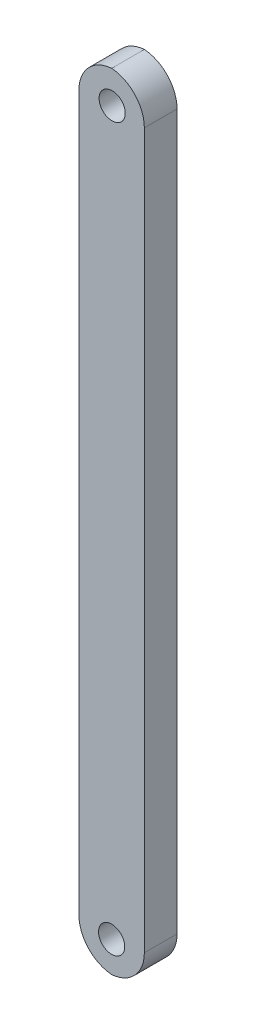
SolidWorks part; units mm, degrees
ref_plane "Front Plane" through (0, 0, 0) normal (0, 0, 1) x (1, 0, 0)
ref_plane "Top Plane" through (0, 0, 0) normal (0, 1, 0) x (1, 0, 0)
ref_plane "Right Plane" through (0, 0, 0) normal (1, 0, 0) x (0, 0, -1)
sketch "Sketch3" plane through (0, 0, 0) normal (0, 0, 1) x (1, 0, 0)
  line L0 (12.7, 0) -> (-12.7, 0)
  line L1 (-12.7, -228.6) -> (-12.7, 228.6)
  line L2 (13.97, 0) -> (-13.97, 0) construction
  line L3 (12.7, -228.6) -> (12.7, 228.6)
  point P4 (0, 0)
  point P9 (-12.7, 0)
  point P11 (12.7, 0)
sketch "Sketch5" plane through (0, 0, 0) normal (0, 0, 1) x (1, 0, 0)
  line L0 (-12.7, 228.6) -> (12.7, 228.6)
  line L1 (-12.7, -228.6) -> (12.7, -228.6)
sketch "Sketch7" plane through (0, 0, 0) normal (0, 0, 1) x (1, 0, 0)
  line L1 (37.3, -371.4) -> (-12.7, -371.4)
  line L2 (37.3, -371.4) -> (37.3, 228.6)
  line L3 (37.3, 228.6) -> (-12.7, 228.6)
  line L4 (-12.7, -371.4) -> (-12.7, 228.6)
  line L5 (37.3, -371.4) -> (-12.7, 228.6) construction
  line L6 (37.3, 228.6) -> (-12.7, -371.4) construction
extrude "Boss-Extrude1" add sketch "Sketch7" along normal mid plane 25
fillet "Fillet1" radius 27 4 edges at (37.3, -371.4, 0) (-12.7, -371.4, 0) (-12.7, 228.6, 0) (37.3, 228.6, 0)
sketch "Sketch8" plane through (0, 0, 12.5) normal (0, 0, 1) x (1, 0, 0)
  line L0 (12.7, -228.6) -> (12.7, 228.6) construction
  circle A0 centre (12.7, 203.9011) radius 10
extrude "Cut-Extrude1" cut sketch "Sketch8" against normal through all
sketch "Sketch9" plane through (0, 0, 12.5) normal (0, 0, 1) x (1, 0, 0)
  line L0 (-12.7, -347.9282) -> (37.3, -347.9282) construction
  line L1 (-12.7, 201.6) -> (-12.7, -344.4) construction
  line L2 (37.3, -344.4) -> (37.3, 201.6) construction
  circle A0 centre (12.3, -347.9282) radius 10
  point P8 (12.3, -444.2772)
  point P9 (12.3, -347.9282)
extrude "Cut-Extrude2" cut sketch "Sketch9" against normal through all
